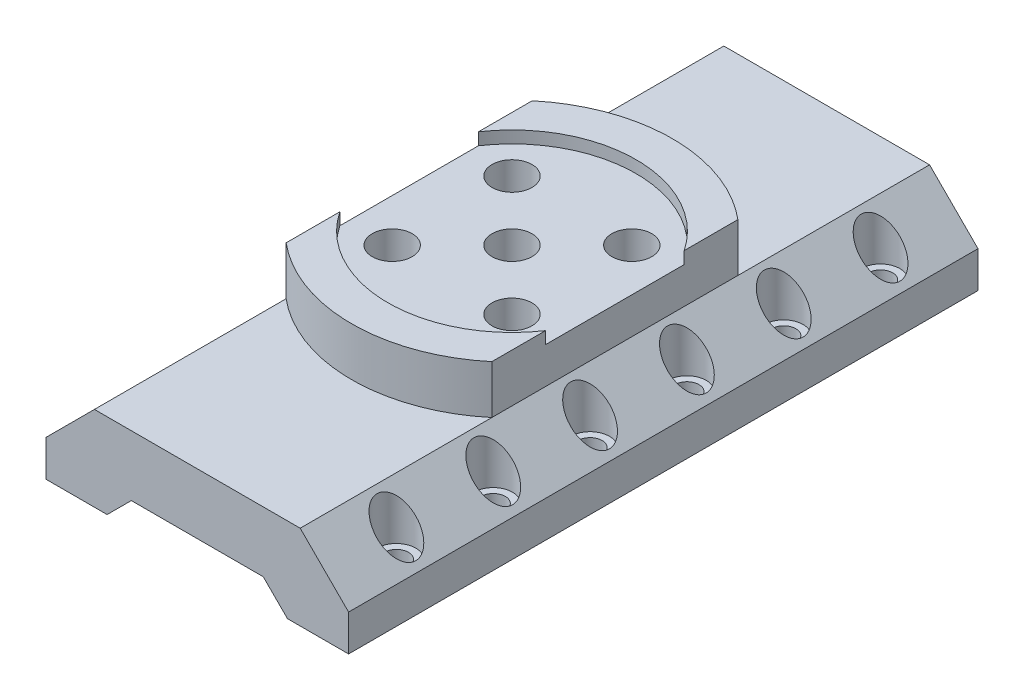
SolidWorks part; units mm, degrees
note: The reader was unsure of these and kept them because the rebuilt part matched: shared geometry of "Sketch12<3>".
ref_plane "Front Plane" through (0, 0, 0) normal (0, 0, 1) x (1, 0, 0)
ref_plane "Top Plane" through (0, 0, 0) normal (0, 1, 0) x (1, 0, 0)
ref_plane "Right Plane" through (0, 0, 0) normal (1, 0, 0) x (0, 0, -1)
sketch "Sketch1" plane through (0, 0, 0) normal (0, 1, 0) x (1, 0, 0)
  line L1 (-12.5, -26) -> (12.5, -26)
  line L2 (-12.5, -26) -> (-12.5, 26)
  line L3 (-12.5, 26) -> (12.5, 26)
  line L4 (12.5, -26) -> (12.5, 26)
  line L5 (-12.5, -26) -> (12.5, 26) construction
  line L6 (-12.5, 26) -> (12.5, -26) construction
  point P0 (0, 0)
  dimension "D1" = 25
  dimension "D2" = 52
extrude "Boss-Extrude1" add sketch "Sketch1" along normal blind 7
sketch "Sketch2" plane through (0, 7, 0) normal (0, 1, 0) x (1, 0, 0)
  line L0 (-10.45, -20) -> (10.45, -20) construction
  line L1 (-12.5, -26) -> (12.5, -26) construction
  circle A0 centre (-10.45, -20) radius 1
  circle A1 centre (10.45, -20) radius 1
  point P4 (0, -20)
  dimension "D1" = 2
  dimension "D2" = 20.9
  dimension "D3" = 6
extrude "Cut-Extrude1" cut sketch "Sketch2" against normal through all
pattern_linear "LPattern1" count 6 spacing 8 along (0, 0, -1) of "Cut-Extrude1"
sketch "Sketch9" plane through (0, 7, 0) normal (0, 1, 0) x (1, 0, 0)
  circle A0 centre (-10.45, 20) radius 1.65
  circle A2 centre (10.45, 20) radius 1.6
  dimension "D1" = 3.3
  dimension "D2" = 3.2
extrude "Cut-Extrude3" cut sketch "Sketch9" against normal blind 4.25
pattern_linear "LPattern2" count 6 spacing 8 along (0, 0, 1) of "Cut-Extrude3"
chamfer "Chamfer2" distance 4 angle 45 2 edges at (-12.5, 7, 0) (12.5, 7, 0)
sketch "Sketch10" plane through (0, 0, 0) normal (0, -1, 0) x (1, 0, 0)
  line L0 (12.5, -26) -> (-12.5, -26) construction
  line L1 (-7.45, -26) -> (7.45, -26)
  line L2 (-7.45, -26) -> (-7.45, 26)
  line L3 (-7.45, 26) -> (7.45, 26)
  line L4 (7.45, -26) -> (7.45, 26)
  line L5 (-12.5, 26) -> (12.5, 26) construction
  circle A0 centre (10.45, 20) radius 1 construction
  circle A1 centre (-10.45, 20) radius 1 construction
  dimension "D1" = 3
  dimension "D2" = 3
extrude "Cut-Extrude4" cut sketch "Sketch10" against normal blind 2
chamfer "Chamfer3" distance 2 angle 45 2 edges at (7.45, 2, 0) (-7.45, 2, 0)
sketch "Sketch12" plane through (0, 7, 0) normal (0, 1, 0) x (1, 0, 0)
  line L0 (-8.5, 26) -> (-8.5, -26) construction
  line L1 (-8.5, 26) -> (-8.5, -26)
  line L2 (8.5, -26) -> (8.5, 26) construction
  line L3 (8.5, -26) -> (8.5, 26)
  circle A0 centre (0, 0) radius 10.25
  circle A1 centre (0, 0) radius 13.25
  line M3 (-8.5, 26) -> (-8.5, -26)
  line M5 (8.5, -26) -> (8.5, 26)
  dimension "D1" = 20.5
  dimension "D2" = 3
extrude "Boss-Extrude2" add sketch "Sketch12" along normal blind 3 contours A1 L1 A0 M5 | L1 A1 A0 M3 | A1 L3 A0 M3 | L3 A1 A0 M5 | L1 A0 | L3 A0
extrude "Boss-Extrude3" add sketch "Sketch12<3>" along normal blind 4 contours A1 L1 A0 M5 | A1 L3 A0 M3
sketch "Sketch12<3>" plane through (0, 7, 0) normal (0, 1, 0) x (1, 0, 0) same geometry as "Sketch12"
sketch "Sketch13" plane through (0, 10, 0) normal (0, 1, 0) x (1, 0, 0)
  line L0 (-4.9497, 4.9497) -> (0, 0) construction
  line L1 (0, 0) -> (-7, 0) construction
  circle A0 centre (0, 0) radius 7 construction
  circle A1 centre (-4.9497, 4.9497) radius 1.65
  circle A2 centre (4.9497, 4.9497) radius 1.65
  circle A3 centre (4.9497, -4.9497) radius 1.65
  circle A4 centre (-4.9497, -4.9497) radius 1.65
  circle A5 centre (0, 0) radius 1.65
  point P15 (0, 0)
  dimension "D2" = 3.3
  dimension "D3" = 14
  dimension "D1" = 45
  dimension "D4" = 4
extrude "Cut-Extrude5" cut sketch "Sketch13" against normal blind 3
sketch "Sketch14" plane through (0, 7, 0) normal (0, 1, 0) x (1, 0, 0)
  circle A0 centre (-4.9497, 4.9497) radius 3
  circle A1 centre (4.9497, 4.9497) radius 3
  circle A2 centre (4.9497, -4.9497) radius 3
  circle A3 centre (-4.9497, -4.9497) radius 3
  circle A4 centre (0, 0) radius 3
  point P12 (0, 0)
  dimension "D1" = 6
  dimension "D2" = 4
extrude "Cut-Extrude6" cut sketch "Sketch14" against normal up to next
